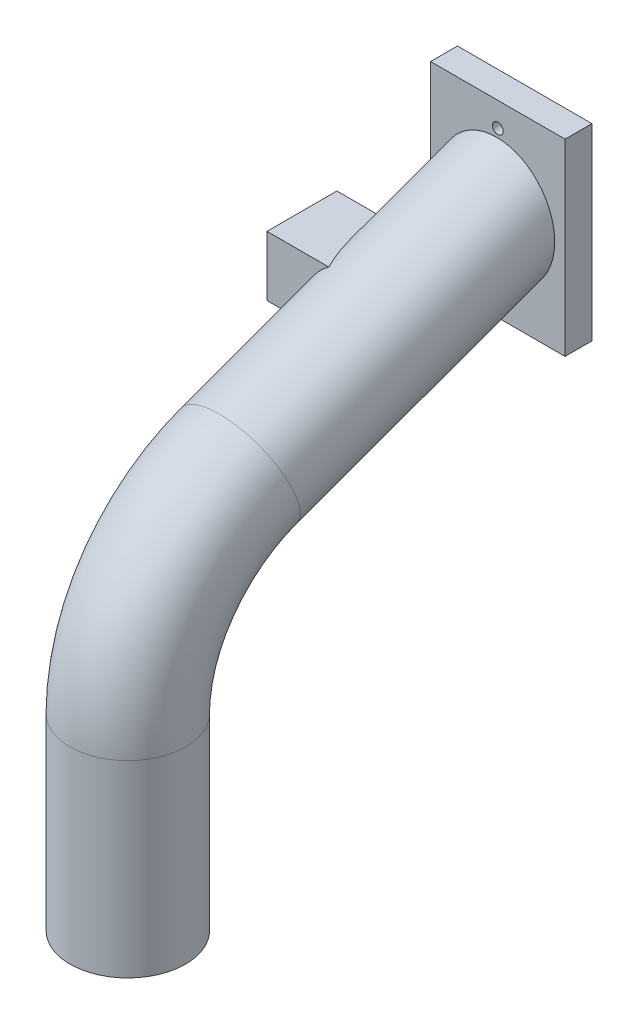
SolidWorks part; units mm, degrees
ref_plane "Plan de face" through (0, 0, 0) normal (0, 0, 1) x (1, 0, 0)
ref_plane "Plan de dessus" through (0, 0, 0) normal (0, 1, 0) x (1, 0, 0)
ref_plane "Plan de droite" through (0, 0, 0) normal (1, 0, 0) x (0, 0, -1)
sketch "Esquisse1" plane through (0, 0, 0) normal (0, 0, 1) x (1, 0, 0)
  line L0 (-5.1867, -35.7264) -> (-5.1867, -30.7264)
  line L1 (-30.1867, 34.2736) -> (19.8133, 34.2736)
  line L2 (-30.1867, 34.2736) -> (-30.1867, -35.7264)
  line L3 (-30.1867, -35.7264) -> (19.8133, -35.7264)
  line L4 (19.8133, 34.2736) -> (19.8133, -35.7264)
  line L5 (-5.1867, -30.7264) -> (-5.1867, 25.2736)
  line L6 (-5.1867, 34.2736) -> (-5.1867, -0.7264)
  line L8 (19.8133, -35.7264) -> (-30.1867, -35.7264) construction
  line L9 (-5.1867, -0.7264) -> (-5.1867, -35.7264) construction
  line L10 (19.8133, 34.2736) -> (-30.1867, 34.2736) construction
  line L11 (19.8133, 34.2736) -> (19.8133, 20.2736)
  line L12 (19.8133, 20.2736) -> (-30.1867, 20.2736)
  line L13 (19.8133, -23.7264) -> (-30.1867, -23.7264)
  circle A0 centre (-5.1867, 25.2736) radius 2
  circle A1 centre (-5.1867, -30.7264) radius 2
  circle A2 centre (-5.1867, -0.7264) radius 20
  dimension "D4" = 4
  dimension "D5" = 4
  dimension "D7" = 14
  dimension "D10" = 40
  dimension "D1" = 70
  dimension "D2" = 5
  dimension "D3" = 56
  dimension "D6" = 35
  dimension "D8" = 12
  dimension "D9" = 50
extrude "Boss.-Extru.1" add sketch "Esquisse1" along normal blind 10 contours A0 L6 L1 L2 L12 | A1 L5 L13 L2 L3 L0 | A1 L0 L3 L4 L13 L5 | L2 L1 L4 L3 | A0 | A1 | A2 region at (-17.9359, -29.705, 0) region at (7.5626, -29.705, 0) region at (-17.8996, 27.3101, 0)
sketch "Esquisse2" plane through (-30.1867, 0, 0) normal (-1, 0, 0) x (0, 0, 1)
  line L0 (10, -35.7264) -> (31.7291, 23.9739) construction
  line L2 (10, 34.2736) -> (10, -35.7264) construction
  dimension "D1" = 20
ref_plane "Plan3" through (0, -7.3931, 20.3125) normal (0, -0.342, 0.9397) x (1, 0, 0)
sketch "Esquisse12" plane through (0, 0, 10) normal (0, 0, 1) x (1, 0, 0)
  line L0 (-5.5545, 19.2702) -> (-5.5545, -20.723) construction
  line L1 (-25.1867, -0.7264) -> (14.8133, -0.7264) construction
  circle A0 centre (-5.1867, -0.7264) radius 20 construction
sketch "Esquisse13" plane through (0, -7.3931, 20.3125) normal (0, -0.342, 0.9397) x (1, 0, 0)
  line L0 (-5.5545, 21.5283) -> (-5.5545, -16.0531) construction
  circle A0 centre (-5.5545, 2.7376) radius 20
  circle A1 centre (-5.5545, 2.7376) radius 21.5
extrude "Boss.-Extru.2" add sketch "Esquisse13" against normal up to surface and the other way blind 90 up to face at (-3.1867, 25.2736, 10)
sketch "Esquisse14" plane through (0, 0, 0) normal (0, 0, -1) x (-1, 0, 0)
  line L0 (5.5545, 19.2702) -> (5.5545, -20.723) construction
  circle A0 centre (5.5545, -0.7264) radius 20
sketch "Esquisse15" plane through (0, 34.2736, 0) normal (0, 1, 0) x (1, 0, 0)
  line L1 (-30.1867, 0) -> (18.9809, 0)
  line L2 (-30.1867, 0) -> (-30.1867, 8.2642)
  line L3 (-30.1867, 8.2642) -> (18.9809, 8.2642)
  line L4 (18.9809, 0) -> (18.9809, 8.2642)
ref_plane "Plan9" through (0, -38.1749, 104.8848) normal (0, -0.342, 0.9397) x (1, 0, 0)
sketch "Esquisse19" plane through (0, -38.1749, 104.8848) normal (0, -0.342, 0.9397) x (1, 0, 0)
  line L0 (-5.5545, 21.5283) -> (-5.5545, -16.0531) construction
  line L3 (-5.5546, -60.2423) -> (33.2952, -60.2423)
  circle A0 centre (-5.5545, 2.7376) radius 20
  circle A1 centre (-5.5545, 2.7376) radius 21.5
revolve "Révolution5" add sketch "Esquisse19" angle 70 about L3 region at (-26.4464, -35.6025, 105.8211)
sketch "Esquisse21" plane through (0, 0, 0) normal (1, 0, 0) x (0, 0, -1)
  line L0 (-168.7606, -94.7842) -> (0, -94.7842) construction
  line L1 (0, -94.7842) -> (0, 34.2736) construction
sketch "Esquisse23" plane through (0, -94.7842, 0) normal (0, -1, 0) x (1, 0, 0)
  line L0 (-5.5546, 167.2606) -> (-5.5546, 127.2606) construction
  line L1 (-25.5545, 147.2606) -> (14.4455, 147.2606) construction
  circle A0 centre (-5.5545, 147.2606) radius 20 construction
  circle A1 centre (-5.5546, 147.2606) radius 20
  circle A2 centre (-5.5546, 147.2606) radius 21.5
extrude "Boss.-Extru.3" add sketch "Esquisse23" along normal blind 70
ref_plane "Plan10" through (-27.1867, 0, 0) normal (-1, 0, 0) x (0, 0, 1)
sketch "Esquisse24" plane through (-27.1867, 0, 0) normal (-1, 0, 0) x (0, 0, 1)
  line L0 (34.8601, -3) -> (34.8601, 0)
  line L1 (34.8601, -3) -> (57.8601, -3)
  line L2 (34.8601, -3) -> (34.8601, -19.3)
  line L3 (34.8601, -19.3) -> (57.8601, -19.3)
  line L4 (57.8601, -3) -> (57.8601, -19.3)
  line L5 (31.8601, 0) -> (60.8601, 0)
  line L6 (31.8601, 0) -> (31.8601, -22.3)
  line L7 (31.8601, -22.3) -> (60.8601, -22.3)
  line L8 (60.8601, 0) -> (60.8601, -22.3)
  line L9 (34.8601, 0) -> (34.8601, -22.3)
  dimension "D1" = 23
  dimension "D2" = 16.3
  dimension "D3" = 3
  dimension "D4" = 3
  dimension "D5" = 3
  dimension "D6" = 3
extrude "Enlèv. mat.-Extru.1" cut sketch "Esquisse24" against normal blind 10 contours L4 L1 L2 L3 region at (-27.1867, -11.15, 46.3601)
sketch "Esquisse27" plane through (-27.1867, 0, 0) normal (-1, 0, 0) x (0, 0, 1)
  line L0 (34.8601, 0) -> (34.8601, -22.3)
  line L1 (34.8601, -3) -> (57.8601, -3)
  line L2 (34.8601, -3) -> (34.8601, -19.3)
  line L3 (34.8601, -19.3) -> (57.8601, -19.3)
  line L4 (57.8601, -3) -> (57.8601, -19.3)
  line L5 (60.8601, -22.3) -> (31.8601, -22.3)
  line L6 (60.8601, -22.3) -> (60.8601, 0)
  line L7 (60.8601, 0) -> (31.8601, 0)
  line L8 (31.8601, -22.3) -> (31.8601, 0)
  dimension "D1" = 3
  dimension "D2" = 3
  dimension "D3" = 3
  dimension "D4" = 3
extrude "Boss.-Extru.4" add sketch "Esquisse27" along normal blind 13 and the other way up to surface separate body contours L6 L7 L0 L1 L4 L3 L5 region at (-27.1867, -0.3425, 47.8601) other way up to face at (-5.5545, -23.6062, 10)
sketch "Esquisse28" plane through (0, 0, 34.8601) normal (0, 0, -1) x (-1, 0, 0)
  line L0 (21.6692, -3) -> (40.1867, -3) construction
  line L1 (29.1385, -3) -> (33.1385, -3)
  line L2 (29.1385, -3) -> (29.1385, -7)
  line L3 (29.1385, -7) -> (33.1385, -7)
  line L4 (33.1385, -3) -> (33.1385, -7)
  line L5 (25.1027, -19.3) -> (40.1867, -19.3) construction
  line L6 (34.9385, -3) -> (38.9385, -3)
  line L7 (34.9385, -3) -> (34.9385, -7)
  line L8 (34.9385, -7) -> (38.9385, -7)
  line L9 (38.9385, -3) -> (38.9385, -7)
  line L10 (29.1385, -19.3) -> (33.1385, -19.3)
  line L11 (29.1385, -19.3) -> (29.1385, -15.3)
  line L12 (29.1385, -15.3) -> (33.1385, -15.3)
  line L13 (33.1385, -19.3) -> (33.1385, -15.3)
  line L14 (27.0272, -19.3) -> (40.1867, -19.3) construction
  line L15 (34.9385, -19.3) -> (38.9385, -19.3)
  line L16 (34.9385, -19.3) -> (34.9385, -15.3)
  line L17 (34.9385, -15.3) -> (38.9385, -15.3)
  line L18 (38.9385, -19.3) -> (38.9385, -15.3)
  dimension "D1" = 4
  dimension "D2" = 4
  dimension "D3" = 4
  dimension "D4" = 4
  dimension "D5" = 4
  dimension "D6" = 4
  dimension "D7" = 4
  dimension "D8" = 4
  dimension "D9" = 1.8
  dimension "D10" = 1.8
extrude "Boss.-Extru.5" add sketch "Esquisse28" against normal up to surface (23 mm away) up to face at (-32.6425, -11.0104, 57.8601)
sketch "Esquisse7" plane through (0, 0, 10) normal (0, 0, 1) x (1, 0, 0)
  line L0 (-25.5546, -0.7264) -> (14.4454, -0.7264) construction
  line L1 (-5.5546, -20.7264) -> (-5.5546, 19.2736) construction
  line L3 (-30.1867, 34.2736) -> (19.0775, 34.2736) construction
  circle A0 centre (-5.5546, -0.7264) radius 20 construction
sketch "Esquisse8" plane through (0, 34.2736, 0) normal (0, 1, 0) x (1, 0, 0)
  line L0 (-5.5546, -10) -> (-5.5546, 0) construction
  line L1 (-30.1867, -10) -> (19.0775, -10) construction
  line L2 (-30.1867, 0) -> (19.0775, 0) construction
ref_plane "Plan2" through (-5.5546, 0, 0) normal (1, 0, 0) x (0, 0, -1)
sketch "Esquisse9" plane through (-5.5546, 0, 0) normal (1, 0, 0) x (0, 0, -1)
  line L0 (-10, -0.7264) -> (-37.4926, -16.5993) construction
  line L1 (-10, -20.7264) -> (-10, 19.2736) construction
  line L2 (-10, 34.2736) -> (-10, -35.7264) construction
  dimension "D1" = 120
